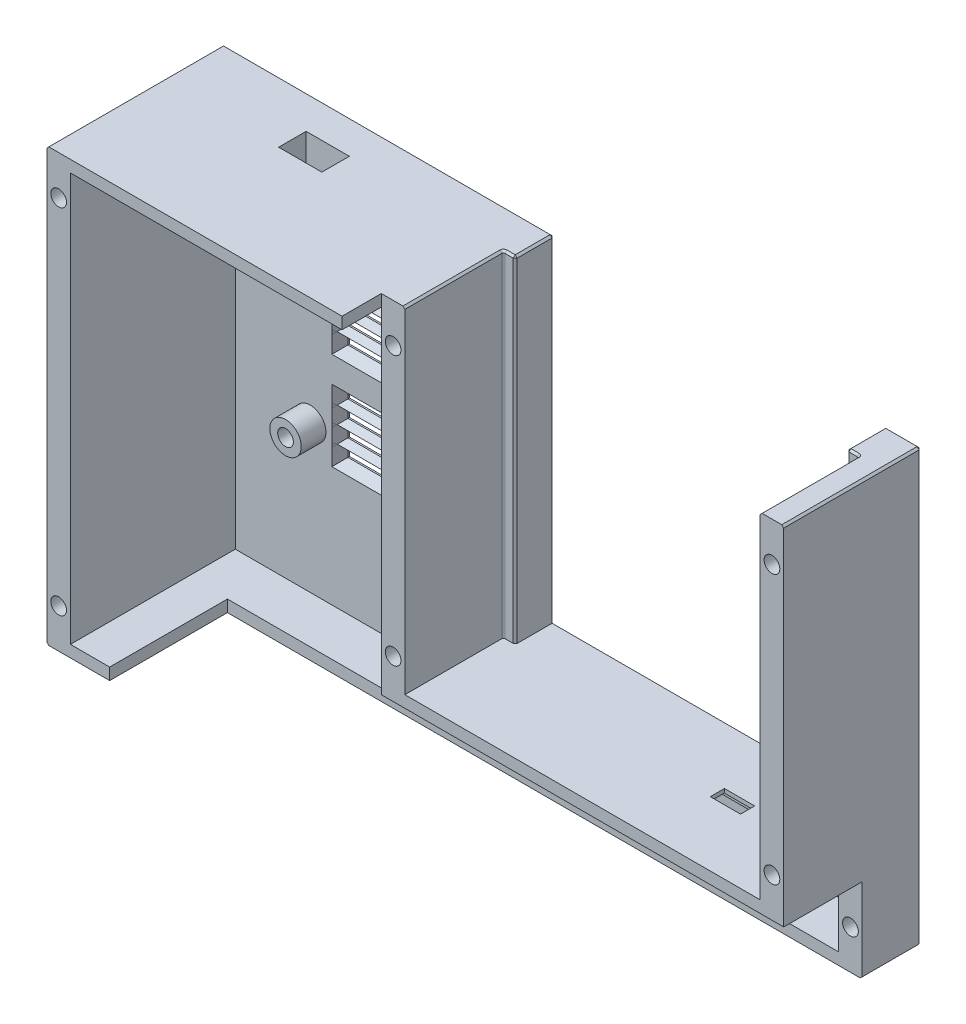
SolidWorks part; units mm, degrees
ref_plane "Plan de face" through (0, 0, 0) normal (0, 0, 1) x (1, 0, 0)
ref_plane "Plan de dessus" through (0, 0, 0) normal (0, 1, 0) x (1, 0, 0)
ref_plane "Plan de droite" through (0, 0, 0) normal (1, 0, 0) x (0, 0, -1)
sketch "Esquisse1" plane through (0, 0, 0) normal (0, 0, 1) x (1, 0, 0)
  line L0 (40.6, 57) -> (0, 57) construction
  line L1 (0, 0) -> (177.7, 0)
  line L2 (0, 0) -> (0, 110)
  line L3 (0, 110) -> (177.7, 110)
  line L4 (177.7, 0) -> (177.7, 110)
  line L6 (11, 16.4285) -> (70.2, 16.4285) construction
  line L7 (11, 16.4285) -> (11, 97.5715) construction
  line L8 (11, 97.5715) -> (70.2, 97.5715) construction
  line L9 (70.2, 16.4285) -> (70.2, 97.5715) construction
  line L10 (11, 16.4285) -> (70.2, 97.5715) construction
  line L11 (11, 97.5715) -> (70.2, 16.4285) construction
  line L12 (171.7, 110) -> (81.2, 110) construction
  line L17 (171.7, 110) -> (171.7, 24.5) construction
  line L18 (171.7, 24.5) -> (81.2, 24.5) construction
  line L19 (81.2, 110) -> (81.2, 24.5) construction
  point P5 (40.6, 57)
  dimension "D1" = 59.2
  dimension "D2" = 81.143
  dimension "D3" = 90.5
  dimension "D4" = 11
  dimension "D5" = 85.5
  dimension "D6" = 11
  dimension "D7" = 6
  dimension "D8" = 110
  dimension "D9" = 53
  dimension "D10" = 177.7
extrude "Boss.-Extru.1" add sketch "Esquisse1" along normal blind 45
sketch "Esquisse2" plane through (0, 110, 0) normal (0, 1, 0) x (1, 0, 0)
  line L0 (168.7, 0) -> (168.7, -9.9)
  line L1 (0, 0) -> (177.7, 0) construction
  line L2 (168.7, -9.9) -> (171.7, -9.9)
  line L3 (171.7, -9.9) -> (171.7, -35)
  line L4 (171.7, -35) -> (81.2, -35)
  line L5 (81.2, -35) -> (81.2, -9.9)
  line L6 (81.2, -9.9) -> (84.2, -9.9)
  line L7 (84.2, -9.9) -> (84.2, 0)
  line L8 (84.2, 0) -> (168.7, 0)
  line L9 (168.7, -9.9) -> (84.2, -9.9) construction
  line L10 (171.7, 0) -> (171.7, -9.9) construction
  line L11 (81.2, 0) -> (81.2, -9.9) construction
  dimension "D1" = 84.5
  dimension "D2" = 9.9
  dimension "D3" = 35
extrude "Enlèv. mat.-Extru.1" cut sketch "Esquisse2" against normal up to vertex (85.5 mm away) up to point (81.2, 24.5, 0)
sketch "Esquisse3" plane through (0, 0, 45) normal (0, 0, 1) x (1, 0, 0)
  line L0 (0, 0) -> (0, 110) construction
  line L1 (6, 107) -> (75.2, 107)
  line L2 (6, 107) -> (6, 3)
  line L3 (6, 3) -> (171.7, 3)
  line L4 (171.7, 21.5) -> (171.7, 3)
  line L5 (177.7, 0) -> (177.7, 110) construction
  line L6 (0, 110) -> (177.7, 110) construction
  line L7 (0, 0) -> (177.7, 0) construction
  line L8 (81.2, 110) -> (81.2, 24.5) construction
  line L10 (75.2, 107) -> (75.2, 21.5)
  line L11 (75.2, 21.5) -> (171.7, 21.5)
  line L13 (171.7, 24.5) -> (81.2, 24.5) construction
  dimension "D1" = 6
  dimension "D2" = 6
  dimension "D3" = 3
  dimension "D4" = 3
  dimension "D5" = 6
  dimension "D6" = 3
ref_plane "Plan1" through (0, 0, 3) normal (0, 0, -1) x (-1, 0, 0)
extrude "Enlèv. mat.-Extru.2" cut sketch "Esquisse3" against normal up to surface (42 mm away) up to plane "Plan1"
sketch "Esquisse4" plane through (0, 0, 45) normal (0, 0, 1) x (1, 0, 0)
  line L1 (75.2, 21.5) -> (177.7, 21.5)
  line L2 (75.2, 21.5) -> (75.2, 110)
  line L3 (75.2, 110) -> (177.7, 110)
  line L4 (177.7, 21.5) -> (177.7, 110)
extrude "Enlèv. mat.-Extru.3" cut sketch "Esquisse4" against normal up to surface (10 mm away) up to face at (126.45, 67.25, 35)
sketch "Esquisse5" plane through (0, 24.5, 0) normal (0, 1, 0) x (1, 0, 0)
  line L0 (126.45, 0) -> (126.45, -16.8) construction
  line L1 (171.7, 0) -> (81.2, 0) construction
  line L2 (126.45, -16.8) -> (146.45, -16.8) construction
  line L3 (146.45, -16.8) -> (156.95, -16.8) construction
  line L4 (146.45, -16.8) -> (135.95, -16.8) construction
  line L5 (177.7, -35) -> (177.7, 0) construction
  line L7 (171.7, -45) -> (177.7, -45) construction
  circle A0 centre (135.95, -16.8) radius 4
  circle A1 centre (156.95, -16.8) radius 4
  circle A2 centre (135.95, -16.8) radius 2
  circle A3 centre (156.95, -16.8) radius 2
  dimension "D4" = 4
  dimension "D5" = 8
  dimension "D1" = 10.5
  dimension "D2" = 31.25
  dimension "D3" = 28.2
extrude "Boss.-Extru.2" add sketch "Esquisse5" against normal blind 8
sketch "Esquisse20" plane through (0, 24.5, 0) normal (0, 1, 0) x (1, 0, 0)
  line L1 (135.95, -16.8) -> (156.95, -16.8) construction
  line L3 (142.6, -15) -> (150.3, -15)
  line L6 (142.6, -15) -> (142.6, -18.6)
  line L19 (142.6, -18.6) -> (150.3, -18.6)
  line L24 (150.3, -15) -> (150.3, -18.6)
  line L25 (142.6, -15) -> (150.3, -18.6) construction
  point P8 (146.45, -16.8)
  point P9 (146.45, -16.8)
  dimension "D1" = 7.7
  dimension "D2" = 3.6
sketch "Esquisse7" plane through (0, 0, 3) normal (0, 0, 1) x (1, 0, 0)
  line L0 (11, 16.4285) -> (70.2, 16.4285) construction
  line L1 (25.1, 85.3285) -> (56.1, 85.3285) construction
  line L2 (25.1, 85.3285) -> (25.1, 40.3285) construction
  line L3 (25.1, 40.3285) -> (56.1, 40.3285) construction
  line L4 (56.1, 85.3285) -> (56.1, 40.3285) construction
  line L7 (40.6, 57) -> (40.6, 85.3285) construction
  circle A0 centre (25.1, 85.3285) radius 4
  circle A1 centre (25.1, 85.3285) radius 2
  circle A2 centre (25.1, 40.3285) radius 4
  circle A3 centre (25.1, 40.3285) radius 2
  circle A4 centre (56.1, 40.3285) radius 2
  circle A5 centre (56.1, 40.3285) radius 4
  circle A6 centre (56.1, 85.3285) radius 2
  circle A7 centre (56.1, 85.3285) radius 4
  dimension "D4" = 4
  dimension "D5" = 8
  dimension "D1" = 45
  dimension "D2" = 31
  dimension "D3" = 23.9
extrude "Boss.-Extru.3" add sketch "Esquisse7" along normal blind 6.3
sketch "Esquisse9" plane through (0, 0, 45) normal (0, 0, 1) x (1, 0, 0)
  line L0 (171.7, 21.5) -> (177.7, 21.5) construction
  line L1 (177.7, 0) -> (16, 0)
  line L2 (177.7, 0) -> (177.7, 21.5)
  line L3 (177.7, 21.5) -> (171.7, 21.5)
  line L4 (16, 0) -> (16, 3)
  line L5 (6, 107) -> (6, 3) construction
  line L6 (16, 3) -> (171.7, 3)
  line L7 (6, 3) -> (171.7, 3) construction
  line L8 (171.7, 3) -> (171.7, 21.5)
  dimension "D1" = 10
extrude "Enlèv. mat.-Extru.6" cut sketch "Esquisse9" against normal blind 30
sketch "Esquisse12" plane through (0, 0, 3) normal (0, 0, 1) x (1, 0, 0)
  line L0 (40.6, 107) -> (40.6, 3) construction
  line L1 (75.2, 107) -> (6, 107) construction
  line L2 (6, 3) -> (171.7, 3) construction
  line L3 (32.1, 70.7) -> (32.1, 72.7) construction
  line L4 (32.1, 75) -> (49.1, 75)
  line L5 (32.1, 75) -> (32.1, 72.7)
  line L6 (32.1, 72.7) -> (49.1, 72.7)
  line L7 (49.1, 75) -> (49.1, 72.7)
  line L8 (32.1, 70.7) -> (49.1, 70.7)
  line L9 (32.1, 70.7) -> (32.1, 68.4)
  line L10 (32.1, 68.4) -> (49.1, 68.4)
  line L11 (49.1, 70.7) -> (49.1, 68.4)
  line L12 (32.1, 66.4) -> (49.1, 66.4)
  line L13 (32.1, 66.4) -> (32.1, 64.1)
  line L14 (32.1, 64.1) -> (49.1, 64.1)
  line L15 (49.1, 66.4) -> (49.1, 64.1)
  line L16 (32.1, 62.1) -> (49.1, 62.1)
  line L17 (32.1, 62.1) -> (32.1, 59.8)
  line L18 (32.1, 59.8) -> (49.1, 59.8)
  line L19 (49.1, 62.1) -> (49.1, 59.8)
  line L20 (32.1, 50.2) -> (49.1, 50.2)
  line L21 (32.1, 50.2) -> (32.1, 47.9)
  line L22 (32.1, 47.9) -> (49.1, 47.9)
  line L23 (49.1, 50.2) -> (49.1, 47.9)
  line L24 (32.1, 45.9) -> (49.1, 45.9)
  line L25 (32.1, 45.9) -> (32.1, 43.6)
  line L26 (32.1, 43.6) -> (49.1, 43.6)
  line L27 (49.1, 45.9) -> (49.1, 43.6)
  line L28 (32.1, 41.6) -> (49.1, 41.6)
  line L29 (32.1, 41.6) -> (32.1, 39.3)
  line L30 (32.1, 39.3) -> (49.1, 39.3)
  line L31 (49.1, 41.6) -> (49.1, 39.3)
  line L32 (32.1, 37.3) -> (49.1, 37.3)
  line L33 (32.1, 37.3) -> (32.1, 35)
  line L34 (32.1, 35) -> (49.1, 35)
  line L35 (49.1, 37.3) -> (49.1, 35)
  line L36 (32.1, 68.4) -> (32.1, 66.4) construction
  line L37 (32.1, 64.1) -> (32.1, 62.1) construction
  line L38 (32.1, 59.8) -> (32.1, 50.2) construction
  line L39 (32.1, 47.9) -> (32.1, 45.9) construction
  line L40 (32.1, 43.6) -> (32.1, 41.6) construction
  line L41 (32.1, 39.3) -> (32.1, 37.3) construction
  line L42 (32.1, 55) -> (40.6, 55) construction
  line L43 (84.2, 110) -> (0, 110) construction
  line L44 (40.6, 75) -> (40.6, 105.3455) construction
  dimension "D1" = 2.3
  dimension "D2" = 2
  dimension "D3" = 35
  dimension "D4" = 17
  dimension "D5" = 104
  dimension "D6" = 180
  dimension "D7" = 104
extrude "Enlèv. mat.-Extru.7" cut sketch "Esquisse12" against normal up to surface (3 mm away) up to face at (107.65, 61.125, 0)
sketch "Esquisse13" plane through (0, 0, 45) normal (0, 0, 1) x (1, 0, 0)
  line L0 (6, 107) -> (0, 107) construction
  line L1 (0, 110) -> (0, 0) construction
  line L2 (6, 3) -> (0, 3) construction
  line L3 (3, 107) -> (3, 100) construction
  line L4 (3, 100) -> (3, 10) construction
  line L6 (75.2, 110) -> (0, 110) construction
  line L7 (0, 0) -> (16, 0) construction
  circle A0 centre (3, 100) radius 2
  circle A1 centre (3, 10) radius 2
  dimension "D3" = 4
  dimension "D1" = 10
  dimension "D2" = 10
extrude "Enlèv. mat.-Extru.8" cut sketch "Esquisse13" against normal blind 5
sketch "Esquisse14" plane through (0, 0, 35) normal (0, 0, 1) x (1, 0, 0)
  line L0 (78.2, 110) -> (78.2, 100) construction
  line L1 (75.2, 110) -> (81.2, 110) construction
  line L2 (78.2, 100) -> (78.2, 31.5) construction
  line L3 (78.2, 31.5) -> (78.2, 21.5) construction
  line L4 (177.7, 21.5) -> (75.2, 21.5) construction
  line L5 (78.2, 21.5) -> (174.7, 21.5) construction
  line L6 (174.7, 21.5) -> (174.7, 31.5) construction
  line L7 (174.7, 31.5) -> (174.7, 100) construction
  line L8 (174.7, 100) -> (174.7, 110) construction
  line L9 (171.7, 110) -> (177.7, 110) construction
  circle A0 centre (78.2, 100) radius 2
  circle A1 centre (78.2, 31.5) radius 2
  circle A2 centre (174.7, 100) radius 2
  circle A3 centre (174.7, 31.5) radius 2
  dimension "D2" = 4
  dimension "D1" = 10
extrude "Enlèv. mat.-Extru.9" cut sketch "Esquisse14" against normal blind 5
sketch "Esquisse15" plane through (0, 0, 15) normal (0, 0, 1) x (1, 0, 0)
  line L0 (174.7, 21.5) -> (174.7, 10) construction
  line L1 (177.7, 21.5) -> (171.7, 21.5) construction
  line L2 (174.7, 10) -> (174.7, 0) construction
  line L3 (16, 0) -> (177.7, 0) construction
  circle A0 centre (174.7, 10) radius 2
  dimension "D2" = 4
  dimension "D1" = 10
extrude "Enlèv. mat.-Extru.10" cut sketch "Esquisse15" against normal blind 5
chamfer "Chanfrein1" distance 1.5 angle 60 32 edges at (40.6, 35, 3) (49.1, 36.15, 3) (40.6, 37.3, 3) (32.1, 36.15, 3) (40.6, 39.3, 3) (49.1, 40.45, 3) (40.6, 41.6, 3) (32.1, 40.45, 3) (40.6, 43.6, 3) (49.1, 44.75, 3) (40.6, 45.9, 3) (32.1, 44.75, 3) (32.1, 49.05, 3) (40.6, 47.9, 3) (49.1, 49.05, 3) (40.6, 50.2, 3) (49.1, 60.95, 3) (40.6, 59.8, 3) (32.1, 60.95, 3) (40.6, 62.1, 3) (49.1, 65.25, 3) (40.6, 64.1, 3) (32.1, 65.25, 3) (40.6, 66.4, 3) (32.1, 69.55, 3) (40.6, 68.4, 3) (40.6, 70.7, 3) (49.1, 69.55, 3) (49.1, 73.85, 3) (40.6, 72.7, 3) (32.1, 73.85, 3) (40.6, 75, 3) first distance on face at (40.6, 73.85, 3)
fillet "Congé1" radius 0.4 2 edges at (171.7, 67.25, 9.9) (81.2, 67.25, 9.9)
chamfer "Chanfrein2" distance 0.5 angle 45 22 edges at (170, 110, 9.9) (171.5828, 110, 10.0172) (171.7, 110, 22.65) (82.9, 110, 9.9) (81.3172, 110, 10.0172) (81.2, 110, 22.65) (0, 0, 22.5) (177.7, 0, 7.5) (0, 110, 22.5) (177.7, 110, 17.5) (168.7, 67.25, 9.9) (168.7, 110, 4.95) (177.7, 55, 0) (88.85, 0, 0) (0, 55, 0) (42.1, 110, 0) (168.7, 67.25, 0) (126.45, 24.5, 0) (84.2, 67.25, 0) (84.2, 110, 4.95) (84.2, 67.25, 9.9) (173.2, 110, 0)
sketch "Esquisse22" plane through (0, 0, 9.3) normal (0, 0, 1) x (1, 0, 0)
  line L0 (32.1, 59.8) -> (49.1, 59.8) construction
  line L1 (70.2, 19.16) -> (11, 19.16)
  line L2 (70.2, 19.16) -> (70.2, 100.44)
  line L4 (11, 19.16) -> (11, 100.44)
  line L5 (70.2, 19.16) -> (11, 100.44) construction
  line L6 (70.2, 100.44) -> (11, 19.16) construction
  line L13 (11, 100.44) -> (70.2, 100.44)
  line L15 (30.69, 100.4545) -> (39.58, 100.4545) construction
  line L16 (30.69, 100.4545) -> (30.69, 95.4545) construction
  line L17 (30.69, 95.4545) -> (39.58, 95.4545) construction
  line L18 (39.58, 100.4545) -> (39.58, 95.4545) construction
  point P0 (40.6, 59.8)
  dimension "D1" = 59.2
  dimension "D2" = 81.28
  dimension "D3" = 8.89
  dimension "D4" = 5
  dimension "D5" = 100.5539
extrude "Boss.-Extru.5" [suppressed] add sketch "Esquisse22" along normal blind 1.5
ref_plane "Plan2" through (25.1, 0, 0) normal (1, 0, 0) x (0, 0, -1)
sketch "Esquisse26" plane through (0, 110, 0) normal (0, 1, 0) x (1, 0, 0)
  line L0 (21.1, -9.3) -> (29.1, -9.3) construction
  line L1 (29.85, -15.8) -> (29.85, -8.8)
  line L2 (29.85, -8.8) -> (40.85, -8.8)
  line L3 (29.85, -15.8) -> (40.85, -15.8)
  line L5 (29.85, -12.3) -> (40.85, -12.3) construction
  line L7 (40.85, -8.8) -> (40.85, -15.8)
  line L9 (35.35, -12.3) -> (40.85, -15.8) construction
  line L11 (25.1, -23.1) -> (25.1, 23.1) construction
  point P3 (29.85, -12.3)
  point P9 (40.85, -12.3)
  dimension "D1" = 7
  dimension "D2" = 11
  dimension "D3" = 3
  dimension "D4" = 10.25
extrude "Enlèv. mat.-Extru.15" cut sketch "Esquisse26" against normal blind 3
sketch "Esquisse27" plane through (0, 110, 0) normal (0, 1, 0) x (1, 0, 0)
  line L0 (29.85, -15.8) -> (40.85, -15.8) construction
  line L6 (29.85, -8.8) -> (29.85, -15.8) construction
  line L14 (29.85, -8.8) -> (40.85, -8.8)
  line L15 (29.85, -8.8) -> (29.85, -15.8)
  line L16 (29.85, -15.8) -> (40.85, -15.8)
  line L17 (40.85, -8.8) -> (40.85, -15.8)
  line L18 (40.85, -8.8) -> (29.85, -8.8) construction
  line L19 (27.85, -6.8) -> (42.85, -6.8)
  line L20 (42.85, -6.8) -> (42.85, -17.8)
  line L21 (27.85, -17.8) -> (42.85, -17.8)
  line L22 (27.85, -6.8) -> (27.85, -17.8)
  dimension "D1" = 2
extrude "Boss.-Extru.9" add sketch "Esquisse27" against normal blind 9.4
extrude "Enlèv. mat.-Extru.17" cut sketch "Esquisse20" against normal blind 10
sketch "Esquisse28" plane through (0, 21.5, 0) normal (0, -1, 0) x (-1, 0, 0)
  line L5 (-150.3, -15) -> (-142.6, -18.6) construction
  line L6 (-152.7, -20.05) -> (-140.2, -20.05)
  line L7 (-152.7, -20.05) -> (-152.7, -13.55)
  line L8 (-152.7, -13.55) -> (-140.2, -13.55)
  line L9 (-140.2, -20.05) -> (-140.2, -13.55)
  line L10 (-152.7, -20.05) -> (-140.2, -13.55) construction
  line L11 (-152.7, -13.55) -> (-140.2, -20.05) construction
  point P0 (-146.45, -16.8)
  point P7 (-146.45, -16.8)
  dimension "D1" = 12.5
  dimension "D2" = 6.5
extrude "Enlèv. mat.-Extru.18" cut sketch "Esquisse28" against normal blind 2
